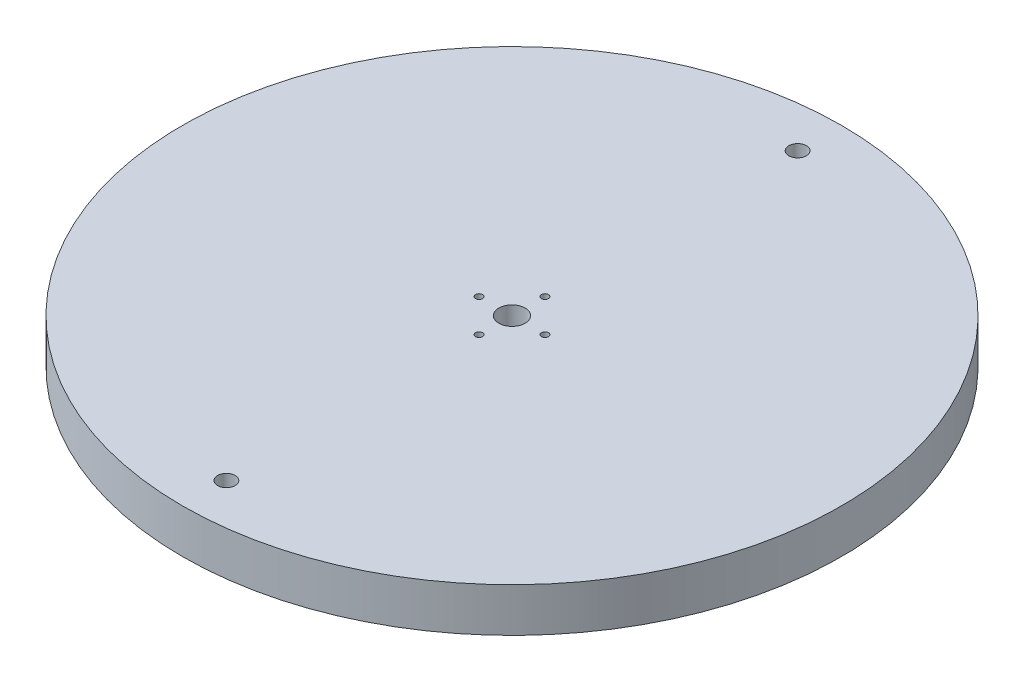
SolidWorks part; units mm, degrees
ref_plane "Plan de face" through (0, 0, 0) normal (0, 0, 1) x (1, 0, 0)
ref_plane "Plan de dessus" through (0, 0, 0) normal (0, 1, 0) x (1, 0, 0)
ref_plane "Plan de droite" through (0, 0, 0) normal (1, 0, 0) x (0, 0, -1)
sketch "Esquisse1" plane through (0, 0, 0) normal (0, 1, 0) x (1, 0, 0)
  circle A0 centre (0, 0) radius 75
  circle A1 centre (0, 0) radius 7.5
  circle A2 centre (0, -7.5) radius 0.8
  circle A3 centre (-7.5, 0) radius 0.8
  circle A4 centre (0, 7.5) radius 0.8
  circle A5 centre (7.5, 0) radius 0.8
  circle A6 centre (0, 0) radius 3
  circle A7 centre (0, 0) radius 65 construction
  circle A8 centre (0, 65) radius 2
  circle A9 centre (0, -65) radius 2
  point P15 (0, 0)
  point P22 (0, 0)
  dimension "D1" = 150
  dimension "D2" = 15
  dimension "D3" = 1.6
  dimension "D5" = 6
  dimension "D7" = 4
  dimension "D6" = 10
  dimension "D4" = 4
  dimension "D8" = 2
extrude "Boss.-Extru.1" add sketch "Esquisse1" along normal blind 10 contours A0 A9 A8 A5 A1 A2 A3 A4 | A5 A1 A4 A3 A2 A6 region at (-72.8787, 0, 0) region at (6.4891, 0, 0)
